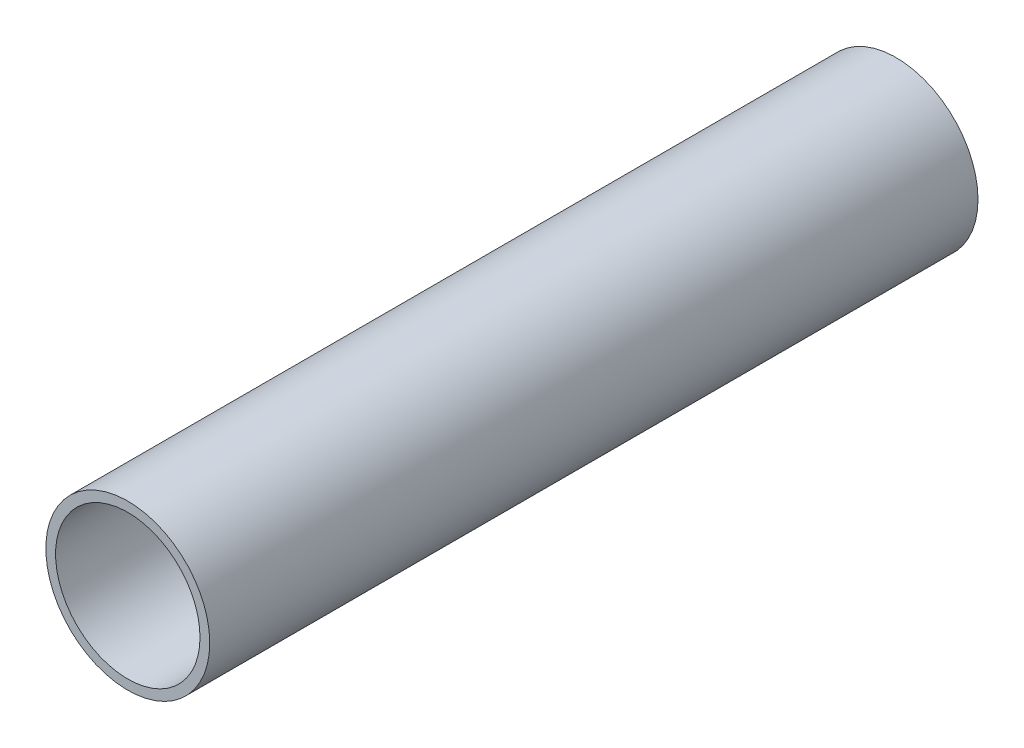
SolidWorks part; units mm, degrees
material "PE Высокой плотности"
ref_plane "Front" through (0, 0, 0) normal (0, 0, 1) x (1, 0, 0)
ref_plane "Top" through (0, 0, 0) normal (0, 1, 0) x (1, 0, 0)
ref_plane "Side" through (0, 0, 0) normal (1, 0, 0) x (0, 0, -1)
sketch "PipeSketch" plane through (0, 0, 0) normal (0, 0, 1) x (1, 0, 0)
  circle A0 centre (0, 0) radius 16
  circle A1 centre (0, 0) radius 14.1
  dimension "OuterDiameter" = 32
  dimension "InnerDiameter" = 28.2
extrude "Extrusion" add sketch "PipeSketch" along normal blind 150
sketch "FilterSketch" plane through (0, 0, 0) normal (0, 0, 1) x (1, 0, 0)
  circle A0 centre (0, 0) radius 16 construction
  dimension "NominalDiameter" = 32
